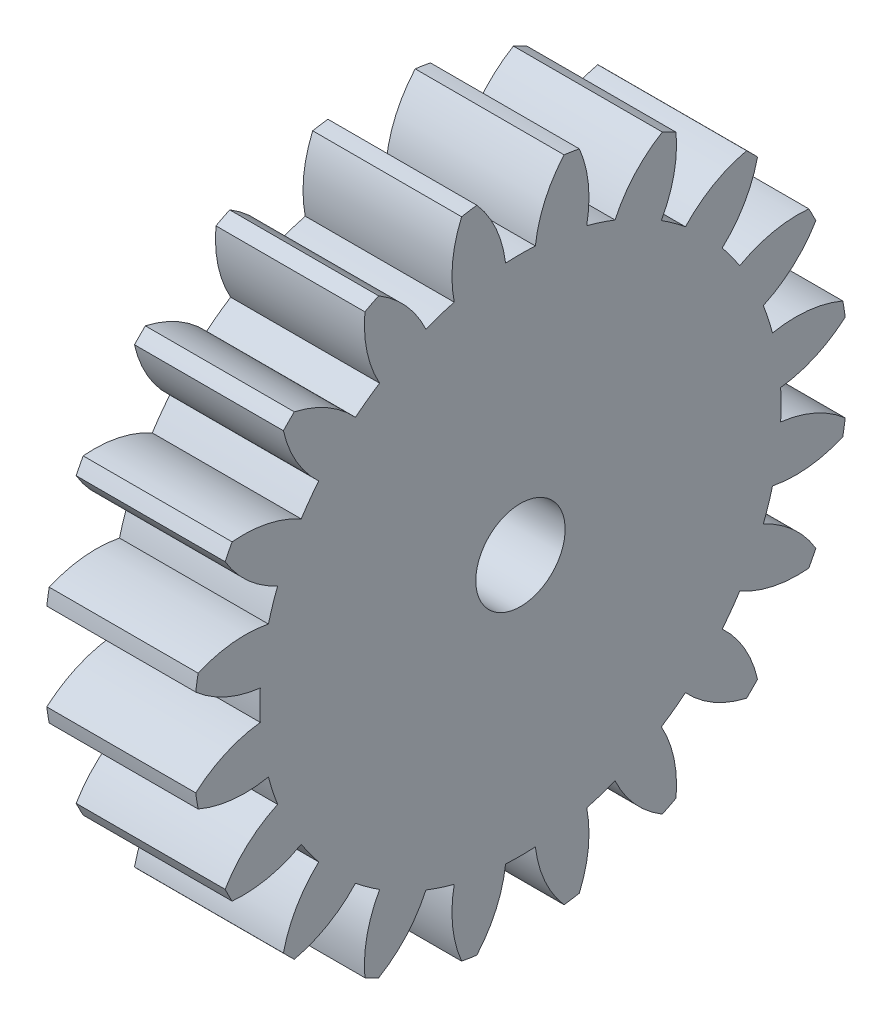
SolidWorks part; units mm, degrees
ref_plane "Plane1" through (0, 0, 0) normal (0, 0, 1) x (1, 0, 0)
ref_plane "Plane2" through (0, 0, 0) normal (0, 1, 0) x (1, 0, 0)
ref_plane "Plane3" through (0, 0, 0) normal (1, 0, 0) x (0, 0, -1)
other "Configuration Table"
sketch "HoldingSke" plane through (0, 0, 0) normal (0, 1, 0) x (1, 0, 0)
  line L0 (0, 0) -> (0.9397, -0.342)
  line L1 (-15, 0) -> (100, 0) construction
  line L2 (0, 0) -> (-2.1039, 2.3779)
  line L3 (0, 0) -> (-11.863, 4.5341)
  line L4 (0, 0) -> (8.1152, 2.9537)
  line L5 (0, 0) -> (-46.8476, -17.4728)
  line L6 (0, 0) -> (-4.1448, -2.7965)
  line L7 (-2.1039, 2.3779) -> (8.6586, 51.2059)
  line L8 (-76.2, 54.61) -> (-75.7, 54.61)
  line L9 (-71.009, 38.7566) -> (-53.1078, 45.2721)
  line L10 (-76.2, 71.12) -> (104.1128, 71.12)
  line L11 (0, 0) -> (-5, 0)
  line L12 (-76.2, 101.6) -> (-76.162, 101.6)
  line L13 (24.9733, 27.94) -> (52.9518, 28.4284)
  line L14 (24.9733, 27.94) -> (24.9743, 27.94)
  line L15 (24.9733, 27.94) -> (100.4006, 29.5858)
  line L16 (-63.627, -1) -> (-12.827, -1)
  circle A0 centre (0, 0) radius 1.5
  circle A1 centre (0, 0) radius 8.749
  circle A2 centre (0, 0) radius 37.5
  circle A3 centre (0, 0) radius 1.5
  dimension "Num_teeth" = 20
  dimension "Pitch_radius" = 180.3128
  dimension "Width" = 5
  dimension "Thickness" = 5
sketch "BasProSke" plane through (0, 0, 0) normal (0, 1, 0) x (1, 0, 0)
  line L0 (-10, 0) -> (60, 0) construction
  line L1 (0, 0) -> (0, 11)
  line L2 (0, 0) -> (5, 0)
  line L3 (5, 0) -> (5, 11)
  line L4 (5, 11) -> (0, 11)
  dimension "Thickness" = 5
  dimension "Diameter" = 22
revolve "Base-Revolve" add sketch "BasProSke" angle 360 about L0
sketch "TooCutSke" plane through (0, 0, 0) normal (1, 0, 0) x (0, 0, -1)
  line L1 (0, 0) -> (0, 107) construction
  line L2 (0, 0) -> (-0.8511, 9.9637) construction
  line L3 (0, 0) -> (-3.1206, 19.7028) construction
  line L4 (-0.8511, 9.9637) -> (-1.5603, 9.8514) construction
  arc A0 (0.4999, 8.7347) -> (-0.4999, 8.7347) centre (0, 0) ccw
  arc A1 (1.4852, 10.9249) -> (-1.4852, 10.9249) centre (0, 0) ccw
  circle A2 centre (0, 0) radius 10 construction
  circle A3 centre (0, 0) radius 9.3969 construction
  arc A4 (-0.4999, 8.7347) -> (-1.4852, 10.9249) centre (-4.4722, 8.2645) ccw
  arc A5 (1.4852, 10.9249) -> (0.4999, 8.7347) centre (4.4722, 8.2645) ccw
extrude "ToothCut" cut sketch "TooCutSke" along normal through all
fillet "Breaks" [suppressed] radius 0.02 tangent propagation no
fillet "RootFillets" [suppressed] radius 0.251
pattern_circular "TeethCuts" count 20 every 18 about axis through (-10, 0, 0) along (1, 0, 0) of "ToothCut", "RootFillets", "Breaks"
sketch "HubNeaOneSke" plane through (0, 0, 0) normal (-1, 0, 0) x (0, 0, 1)
  circle A0 centre (0, 0) radius 8.749
  dimension "Diameter" = 17.498
extrude "HubNearOne" [suppressed] add sketch "HubNeaOneSke" along normal blind 45.0001
sketch "HubNeaBotSke" plane through (0, 0, 0) normal (-1, 0, 0) x (0, 0, 1)
  circle A0 centre (0, 0) radius 8.749
  dimension "Diameter" = 17.498
extrude "HubNearBoth" [suppressed] add sketch "HubNeaBotSke" along normal blind 22.5
ref_plane "FarPln" through (5, 0, 0) normal (1, 0, 0) x (0, 0, -1)
sketch "HubFarSke" plane through (5, 0, 0) normal (1, 0, 0) x (0, 0, -1)
  circle A0 centre (0, 0) radius 8.749
  dimension "Diameter" = 17.498
extrude "HubFar" [suppressed] add sketch "HubFarSke" along normal blind 22.5
sketch "BorSke" plane through (0, 0, 0) normal (1, 0, 0) x (0, 0, -1)
  circle A0 centre (0, 0) radius 1.5
  dimension "Diameter" = 3
extrude "Bore" cut sketch "BorSke" along normal mid plane 100.0001
sketch "KeySke" plane through (0, 0, 0) normal (1, 0, 0) x (0, 0, -1)
  line L0 (-0.6, 0) -> (-0.6, 2)
  line L1 (-0.6, 2) -> (0.6, 2)
  line L2 (0.6, 2) -> (0.6, 0)
  line L3 (0, 0) -> (0, 34) construction
  line L4 (-0.6, 0) -> (0.6, 0)
  dimension "Width" = 1.2
extrude "Keyway" [suppressed] cut sketch "KeySke" along normal mid plane 100.0001
pattern_circular "Keyway2" [suppressed] count 2 every 90 about axis through (-10, 0, 0) along (1, 0, 0)
equation "' \"Module@HoldingSke\" = 6.35"
equation "' \"Num_teeth@HoldingSke\" = 12"
equation "' \"Ap@HoldingSke\" =  20"
equation "' \"Ap@HoldingSke\" = 20"
equation "' \"Width@HoldingSke\" = 0.5 * 25.4"
equation "' \"Hub_dia@HoldingSke\"= 1 * 25.4"
equation "' \"Hub_dia@HoldingSke\" = 1 * 25.4"
equation "' \"Overall_len@HoldingSke\" = 1.0 * 25.4"
equation "' \"Bore@HoldingSke\" = 0.75 * 25.4"
equation "' \"T_dim@HoldingSke\" = 0.1 * 25.4"
equation "' \"Width@KeySke\" = 0.25 * 25.4"
equation "' \"Show_teeth@HoldingSke\" = 13"
equation "' \"Backlash@HoldingSke\" = 0.009 * 25.4"
equation "' \"Addendum_fac@HoldingSke\" = 1.0"
equation "' \"Dedendum_fac@HoldingSke\" = 1.25"
equation "' \"Dedendum_add@HoldingSke\" = 0.00005 * 25.4"
equation "' \"Clearance_fac@HoldingSke\" = 0.25"
equation "\"Pitch@HoldingSke\" = 1 / \"Module@HoldingSke\""
equation "\"Overcut_dia@TooCutSke\" = (\"Num_teeth@HoldingSke\" + 2 * \"Addendum_fac@HoldingSke\") / \"Pitch@HoldingSke\" + 0.002 * 25.4"
equation "\"Pitch_dia@TooCutSke\" = \"Num_teeth@HoldingSke\" / \"Pitch@HoldingSke\""
equation "\"Base_dia@TooCutSke\" = \"Num_teeth@HoldingSke\" / \"Pitch@HoldingSke\" * cos((\"Ap@HoldingSke\"  * 3.14159265 / 180))"
equation "\"Root_dia@TooCutSke\" = (\"Num_teeth@HoldingSke\" + 2) / \"Pitch@HoldingSke\" - 2 * (\"Addendum_fac@HoldingSke\" + \"Dedendum_fac@HoldingSke\") / \"Pitch@HoldingSke\" - \"Dedendum_add@HoldingSke\" * 2"
equation "\"Half_ang@TooCutSke\" = 180 / \"Num_teeth@HoldingSke\""
equation "\"Half_CT@TooCutSke\" = \"Num_teeth@HoldingSke\" / \"Pitch@HoldingSke\" * sin((3.14159265 / 2 / \"Num_teeth@HoldingSke\")) / 2 - 7 * \"Backlash@HoldingSke\" / 4"
equation "\"Flank_rad@TooCutSke\" = \"Num_teeth@HoldingSke\" / \"Pitch@HoldingSke\" / 5"
equation "\"Radius@RootFillets\" = \"Clearance_fac@HoldingSke\" / \"Pitch@HoldingSke\" + \"Dedendum_add@HoldingSke\""
equation "\"Break_rad@Breaks\" = 0.02 / \"Pitch@HoldingSke\""
equation "\"Thickness@HoldingSke\" = \"Width@HoldingSke\""
equation "\"OAL@HoldingSke\" = \"Thickness@HoldingSke\""
equation "\"MHD@HoldingSke\" = (\"Num_teeth@HoldingSke\" + 2) / \"Pitch@HoldingSke\" - 2 * (\"Addendum_fac@HoldingSke\" + \"Dedendum_fac@HoldingSke\")  / \"Pitch@HoldingSke\" - \"Dedendum_add@HoldingSke\" * 2"
equation "\"MBD@HoldingSke\" = (\"Num_teeth@HoldingSke\" + 2) / \"Pitch@HoldingSke\" - 2 * (\"Addendum_fac@HoldingSke\" + \"Dedendum_fac@HoldingSke\")  / \"Pitch@HoldingSke\" - \"Dedendum_add@HoldingSke\" * 2 - 0.002 * 25.4"
equation "\"MHD@HoldingSke\" = ((sgn( \"MHD@HoldingSke\" - \"Hub_dia@HoldingSke\" )-1)*( \"MHD@HoldingSke\" - \"Hub_dia@HoldingSke\" ))/-2+ \"Hub_dia@HoldingSke\""
equation "\"MBD@HoldingSke\" = ((sgn( \"MBD@HoldingSke\" - \"Bore@HoldingSke\" )-1)*( \"MBD@HoldingSke\" - \"Bore@HoldingSke\" ))/-2+ \"Bore@HoldingSke\""
equation "\"OAL@HoldingSke\" = ((sgn( \"OAL@HoldingSke\" - \"Overall_len@HoldingSke\" )+1)*( \"OAL@HoldingSke\" - \"Overall_len@HoldingSke\" ))/2 + \"Overall_len@HoldingSke\" + 0.000002 * 25.4"
equation "\"Num_teeth@TeethCuts\" = int( \"Show_teeth@HoldingSke\" ) + 1"
equation "\"Num_teeth@TeethCuts\" = ((sgn( \"Num_teeth@TeethCuts\" - \"Num_teeth@HoldingSke\" )-1)*( \"Num_teeth@TeethCuts\" - \"Num_teeth@HoldingSke\" ))/-2+ \"Num_teeth@HoldingSke\""
equation "\"Num_teeth@TeethCuts\" = ((sgn( \"Num_teeth@TeethCuts\" - 2.0)+1)*( \"Num_teeth@TeethCuts\" - 2.0))/2 +2.0"
equation "\"Angle@TeethCuts\" = 360.0 / \"Num_teeth@HoldingSke\""
equation "\"Diameter@BasProSke\" = (\"Num_teeth@HoldingSke\" + 2 * \"Addendum_fac@HoldingSke\") / \"Pitch@HoldingSke\""
equation "\"Thickness@BasProSke\"  = \"Thickness@HoldingSke\""
equation "' \"Fillet_rad@BasProSke\" =  \"Thickness@HoldingSke\" * 0.05"
equation "' \"Fillet_rad@BasProSke\" = \"Thickness@HoldingSke\" * 0.05"
equation "\"MHD@HoldingSke\" = ((sgn( \"MHD@HoldingSke\" - \"Root_dia@TooCutSke\" )-1)*( \"MHD@HoldingSke\" - \"Root_dia@TooCutSke\" ))/-2+ \"Root_dia@TooCutSke\""
equation "\"Diameter@HubNeaOneSke\" = \"MHD@HoldingSke\""
equation "\"Length@HubNearOne\" = \"OAL@HoldingSke\" - \"Thickness@BasProSke\""
equation "\"Diameter@HubNeaBotSke\" = \"MHD@HoldingSke\""
equation "\"Length@HubNearBoth\" = ( \"OAL@HoldingSke\" - \"Thickness@BasProSke\" ) / 2.0"
equation "\"Thickness@FarPln\" = \"Thickness@BasProSke\""
equation "\"Diameter@HubFarSke\" = \"MHD@HoldingSke\""
equation "\"Length@HubFar\" = ( \"OAL@HoldingSke\" - \"Thickness@BasProSke\" ) / 2.0"
equation "\"Diameter@BorSke\" = \"MBD@HoldingSke\""
equation "\"D1@Bore\" = \"OAL@HoldingSke\" * 2.0"
equation "\"D1@Keyway\" = \"OAL@HoldingSke\" * 2.0"
equation "\"Offset@KeySke\" = \"T_dim@HoldingSke\" + \"MBD@HoldingSke\" / 2.0"
